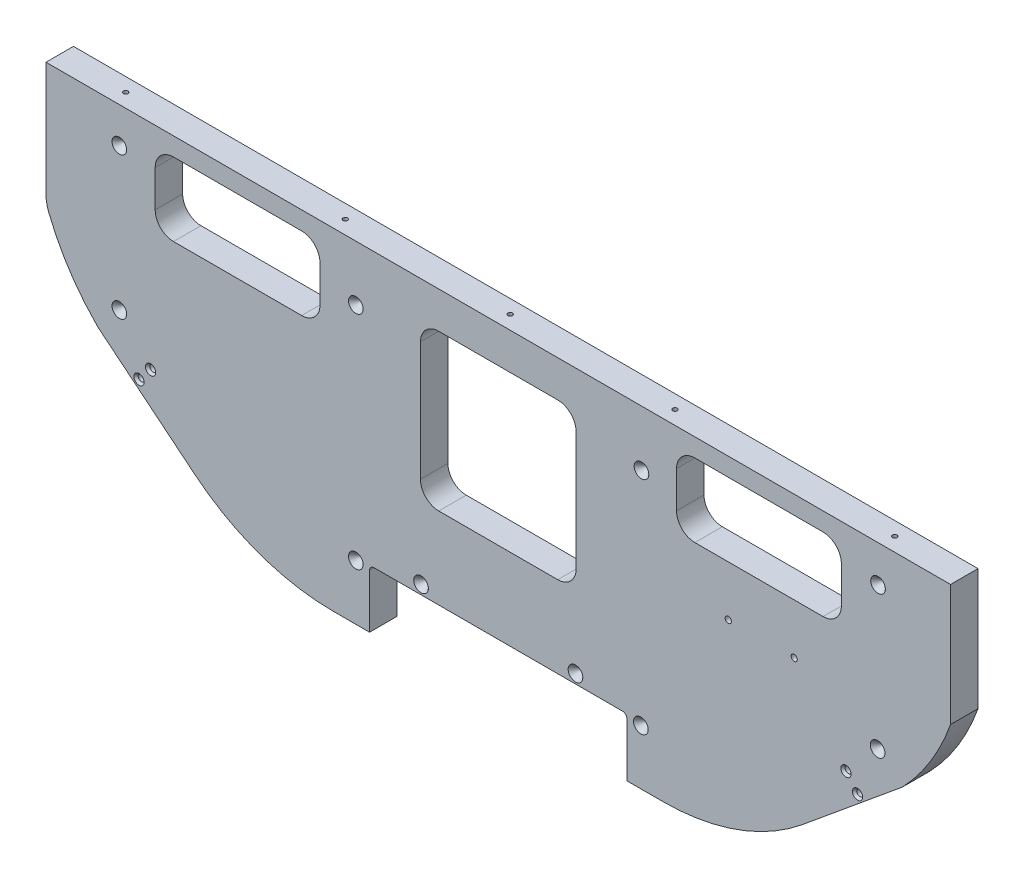
SolidWorks part; units mm, degrees
material "MDF"
ref_plane "Front Plane" through (0, 0, 0) normal (0, 0, 1) x (1, 0, 0)
ref_plane "Top Plane" through (0, 0, 0) normal (0, 1, 0) x (1, 0, 0)
ref_plane "Right Plane" through (0, 0, 0) normal (1, 0, 0) x (0, 0, -1)
sketch "Sketch1" plane through (0, 0, 0) normal (0, 0, 1) x (1, 0, 0)
  line L0 (-394.3667, -87.3125) -> (-394.3667, 23.8125) construction
  line L2 (-618.7884, -233.3625) -> (-593.7567, -233.3625) construction
  line L3 (-394.3667, -87.3125) -> (-394.3667, -3.175)
  line L4 (-497.3744, -199.0142) -> (-427.755, -141.5981)
  line L5 (-709.3267, -233.3625) -> (-593.7567, -233.3625)
  line L6 (-709.3267, -3.175) -> (-709.3267, -233.3625) construction
  line L7 (-1021.7467, -3.175) -> (-396.9067, -3.175) construction
  line L8 (-394.3667, -3.175) -> (-709.3267, -3.175)
  line L9 (-1021.7467, -3.175) -> (-396.9067, -3.175) construction
  line L10 (-976.0267, -152.2395) -> (-918.7391, -199.0142) construction
  line L11 (-1021.7467, -87.3125) -> (-1021.7467, -20.955) construction
  line L12 (-985.5517, -144.4625) -> (-918.7391, -199.0142)
  line L13 (-1021.7467, -87.3125) -> (-1021.7467, -3.175)
  line L14 (-822.3567, -233.3625) -> (-709.3267, -233.3625)
  line L15 (-709.3267, -3.175) -> (-1021.7467, -3.175)
  arc A0 (-427.755, -141.5981) -> (-394.3667, -87.3125) centre (-538.0037, -36.3792) ccw construction
  arc A1 (-593.7567, -233.3625) -> (-497.3744, -199.0142) centre (-593.7567, -80.9625) ccw construction
  arc A2 (-427.755, -141.5981) -> (-394.3667, -87.3125) centre (-538.0037, -36.3792) ccw
  arc A3 (-593.7567, -233.3625) -> (-497.3744, -199.0142) centre (-593.7567, -80.9625) ccw
  arc A4 (-918.7391, -199.0142) -> (-822.3567, -233.3625) centre (-822.3567, -80.9625) ccw construction
  arc A5 (-1021.7467, -87.3125) -> (-985.5517, -144.4625) centre (-878.1098, -36.3792) ccw construction
  arc A6 (-918.7391, -199.0142) -> (-822.3567, -233.3625) centre (-822.3567, -80.9625) ccw
  arc A7 (-1021.7467, -87.3125) -> (-985.5517, -144.4625) centre (-878.1098, -36.3792) ccw
  point P13 (-709.3267, -3.175)
extrude "Boss-Extrude1" add sketch "Sketch1" along normal blind 19.05
hole_wizard "5/64 (0.07813) Diameter Hole1" positions "Sketch2" profile "Sketch3" hole size "5/64" standard "ANSI Inch"
sketch "Sketch2" plane through (-708.0567, 15.875, 6128.5599) normal (0, 1, 0) x (1, 0, 0)
  line L1 (-1.27, 6109.5099) -> (-1.27, 6338.7449) construction
  point P0 (-262.8265, 6157.4524)
  point P6 (-98.7933, 6157.4524)
  point P18 (-262.8265, 6233.6524)
  point P19 (-98.7933, 6233.6524)
  point P22 (-262.8265, 6309.8524)
  point P23 (-98.7933, 6309.8524)
  point P24 (-267.97, 6119.0349)
  point P34 (-115.57, 6119.0349)
  point P37 (-1.27, 6119.0349)
  point P40 (113.03, 6119.0349)
  point P44 (265.43, 6119.0349)
  point P55 (96.2533, 6309.8524)
  point P56 (260.2865, 6309.8524)
  point P59 (96.2533, 6233.6524)
  point P60 (260.2865, 6233.6524)
  point P63 (96.2533, 6157.4524)
  point P64 (260.2865, 6157.4524)
sketch "Sketch3" plane through (-970.8832, 15.875, -28.8925) normal (1, 0, 0) x (0, 0, 1)
  line L0 (0, 0) -> (0, 39.0539)
  line L1 (0, 39.0539) -> (1.5875, 38.1)
  line L2 (1.5875, 38.1) -> (1.5875, 4.0177)
  line L3 (1.5875, 4.0177) -> (5.08, 0)
  line L4 (5.08, 0) -> (0, 0)
  line L5 (-1.5875, 4.0177) -> (-5.08, 0) construction
  line L6 (0, 39.0539) -> (-1.5875, 38.1) construction
  line L7 (0, -6.35) -> (0, 107.95) construction
  dimension "Hole Dia." = 3.175
  dimension "Hole Depth" = 38.1
  dimension "Near C'Sink Dia." = 10.16
  dimension "Near C'Sink Angle" = 82
  dimension "Drill Angle" = 118
hole_wizard "5/64 (0.07813) Diameter Hole2" positions "Sketch4" profile "Sketch5" hole size "5/64" standard "ANSI Inch"
sketch "Sketch4" plane through (-708.0567, 1936.854, 19.05) normal (0, 0, 1) x (-1, 0, 0)
  line L23 (262.8265, 2088.1084) -> (262.8265, 2038.7486)
  line L24 (262.8265, 2038.7486) -> (262.8265, 1989.3888)
  line L25 (262.8265, 1989.3888) -> (262.8265, 2038.7486)
  line L26 (262.8265, 2038.7486) -> (262.8265, 1989.3888)
  line L27 (262.8265, 1989.3888) -> (262.8265, 1940.029)
  line L33 (98.7933, 2170.2165) -> (98.7933, 2131.8519)
  line L35 (98.7933, 2131.8519) -> (98.7933, 2093.4873)
  line L36 (98.7933, 2093.4873) -> (98.7933, 2055.1227)
  line L37 (98.7933, 2055.1227) -> (98.7933, 2016.7581)
  line L38 (98.7933, 2016.7581) -> (98.7933, 1978.3935)
  line L39 (98.7933, 1978.3935) -> (98.7933, 1940.029)
  line L44 (89.2683, 2123.544) -> (53.561, 2123.544)
  line L46 (53.561, 2123.544) -> (17.8537, 2123.544)
  line L47 (17.8537, 2123.544) -> (-17.8537, 2123.544)
  line L48 (-17.8537, 2123.544) -> (-53.561, 2123.544)
  line L49 (-53.561, 2123.544) -> (-89.2683, 2123.544)
  line L53 (0, 2170.2165) -> (-0.3175, 1940.029) construction
  line L55 (-99.3221, 1978.6668) -> (-99.4279, 1940.3024)
  line L56 (-99.2163, 2017.0312) -> (-99.3221, 1978.6668)
  line L57 (-99.1104, 2055.3957) -> (-99.2163, 2017.0312)
  line L58 (-99.0046, 2093.7601) -> (-99.1104, 2055.3957)
  line L59 (-98.8988, 2132.1245) -> (-99.0046, 2093.7601)
  line L60 (-98.7929, 2170.489) -> (-98.8988, 2132.1245)
  line L61 (-263.3243, 1990.1145) -> (-263.4605, 1940.7549)
  line L62 (-263.1882, 2039.4741) -> (-263.3243, 1990.1145)
  line L63 (-263.3243, 1990.1145) -> (-263.1882, 2039.4741)
  line L64 (-263.1882, 2039.4741) -> (-263.3243, 1990.1145)
  line L65 (-263.052, 2088.8338) -> (-263.1882, 2039.4741)
  point P71 (262.8265, 1964.7089)
  point P79 (262.8265, 2063.4285)
  point P95 (98.7933, 2131.8519)
  point P103 (98.7933, 1978.3935)
  point P126 (53.561, 2123.544)
  point P134 (-53.561, 2123.544)
  point P162 (-99.3221, 1978.6668)
  point P166 (-98.8988, 2132.1245)
  point P167 (-263.1201, 2064.1539)
  point P169 (-263.3924, 1965.4347)
sketch "Sketch5" plane through (-444.6643, -28.5807, 19.05) normal (1, 0, 0) x (0, -1, 0)
  line L0 (0, 0) -> (0, 38.6962)
  line L1 (0, 38.6962) -> (0.9923, 38.1)
  line L2 (0.9923, 38.1) -> (0.9923, 4.7024)
  line L3 (0.9923, 4.7024) -> (5.08, 0)
  line L4 (5.08, 0) -> (0, 0)
  line L5 (-0.9923, 4.7024) -> (-5.08, 0) construction
  line L6 (0, 38.6962) -> (-0.9923, 38.1) construction
  line L7 (0, -6.35) -> (0, 107.95) construction
  dimension "Hole Dia." = 1.9845
  dimension "Hole Depth" = 38.1
  dimension "Near C'Sink Dia." = 10.16
  dimension "Near C'Sink Angle" = 82
  dimension "Drill Angle" = 118
sketch "Sketch6" plane through (0, 0, 0) normal (0, 0, -1) x (-1, 0, 0)
  line L1 (797.325, -233.3625) -> (618.7884, -233.3625)
  line L2 (797.325, -233.3625) -> (797.325, -193.04)
  line L3 (797.325, -193.04) -> (618.7884, -193.04)
  line L4 (618.7884, -233.3625) -> (618.7884, -193.04)
extrude "Cut-Extrude1" cut sketch "Sketch6" against normal up to next
fillet "Fillet1" radius 25.4 2 edges at (-985.5517, -144.4625, 9.525) (-1021.7467, -87.3125, 9.525)
hole_wizard "#6 Clearance Hole1" positions "Sketch7" profile "Sketch8" hole size "#6" standard "ANSI Inch" end condition up to next
sketch "Sketch7" plane through (0, 0, 19.05) normal (0, 0, 1) x (1, 0, 0)
  arc A0 (-504.7297, -98.0667) -> (-504.7297, -104.8742) centre (-502.7993, -101.4705) ccw construction
  arc A1 (-550.4497, -98.0667) -> (-550.4497, -104.8742) centre (-548.5193, -101.4705) ccw construction
  point P0 (-502.7993, -101.4705)
  point P2 (-548.5193, -101.4705)
sketch "Sketch8" plane through (-502.7993, -101.4705, 19.05) normal (1, 0, 0) x (0, -1, 0)
  line L0 (0, 0) -> (0, 19.05)
  line L1 (0, 19.05) -> (2.1526, 19.05)
  line L2 (2.1526, 19.05) -> (2.1526, 0)
  line L5 (2.1526, 0) -> (0, 0)
  line L11 (0, -6.35) -> (0, 107.95) construction
  dimension "Thru Hole Dia." = 4.3053
  dimension "Thru Hole Depth" = 19.05
hole_wizard "CSK for #6 Flat Head Machine Screw (100)1" positions "Sketch9" profile "Sketch10" countersink size "#6" standard "ANSI Inch" end condition up to next
sketch "Sketch9" plane through (0, 0, 19.05) normal (0, 0, 1) x (1, 0, 0)
  point P0 (-957.2382, -161.4319)
  point P3 (-949.206, -151.5944)
  point P6 (-466.9052, -151.5924)
  point P9 (-458.8731, -161.4298)
sketch "Sketch10" plane through (-957.2382, -161.4319, 19.05) normal (1, 0, 0) x (0, -1, 0)
  line L0 (0, 0) -> (0, 19.05)
  line L1 (0, 19.05) -> (2.1526, 19.05)
  line L2 (2.1526, 19.05) -> (2.1526, 1.5998)
  line L3 (2.1526, 1.5998) -> (3.5433, 0)
  line L5 (3.5433, 0) -> (0, 0)
  line L6 (-2.1526, 1.5998) -> (-3.5433, 0) construction
  line L11 (0, -6.35) -> (0, 107.95) construction
  dimension "Thru Hole Dia." = 4.3053
  dimension "Thru Hole Depth" = 19.05
  dimension "Near C'Sink Dia." = 7.0866
  dimension "Near C'Sink Angle" = 82
sketch "Sketch12" plane through (0, 0, 19.05) normal (0, 0, 1) x (1, 0, 0)
  line L0 (-708.0567, -193.04) -> (-708.0567, -3.175) construction
  line L1 (-797.325, -193.04) -> (-618.7884, -193.04) construction
  line L2 (-394.3667, -3.175) -> (-1021.7467, -3.175) construction
  line L3 (-970.8832, -27.8549) -> (-806.85, -27.8549) construction
  line L4 (-806.85, -41.5396) -> (-806.85, -27.8549) construction
  line L5 (-584.3968, -15.875) -> (-470.0968, -15.875)
  line L6 (-831.7166, -66.675) -> (-946.0166, -66.675)
  line L7 (-831.7166, -66.675) -> (-831.7166, -15.875)
  line L8 (-831.7166, -15.875) -> (-946.0166, -15.875)
  line L9 (-946.0166, -66.675) -> (-946.0166, -15.875)
  line L10 (-831.7166, -66.675) -> (-946.0166, -15.875) construction
  line L11 (-831.7166, -15.875) -> (-946.0166, -66.675) construction
  line L12 (-470.0968, -66.675) -> (-470.0968, -15.875)
  line L13 (-584.3968, -66.675) -> (-470.0968, -66.675)
  line L14 (-584.3968, -66.675) -> (-584.3968, -15.875)
  line L15 (-394.3667, -3.175) -> (-1021.7467, -3.175) construction
  line L16 (-654.0817, -136.525) -> (-762.0317, -136.525)
  line L17 (-654.0817, -136.525) -> (-654.0817, -28.575)
  line L18 (-654.0817, -28.575) -> (-762.0317, -28.575)
  line L19 (-762.0317, -136.525) -> (-762.0317, -28.575)
  line L20 (-654.0817, -136.525) -> (-762.0317, -28.575) construction
  line L21 (-654.0817, -28.575) -> (-762.0317, -136.525) construction
  point P9 (-888.8666, -27.8549)
  point P10 (-888.8666, -41.275)
  point P20 (-708.0567, -82.55)
  dimension "D1" = 114.3
  dimension "D2" = 50.8
  dimension "D3" = 12.7
  dimension "D4" = 107.95
  dimension "D5" = 107.95
  dimension "D6" = 25.4
extrude "Cut-Extrude2" cut sketch "Sketch12" against normal through all
fillet "Fillet2" radius 12.7 12 edges at (-584.3968, -66.675, 9.525) (-584.3968, -15.875, 9.525) (-470.0968, -15.875, 9.525) (-470.0968, -66.675, 9.525) (-654.0817, -136.525, 9.525) (-654.0817, -28.575, 9.525) (-762.0317, -28.575, 9.525) (-762.0317, -136.525, 9.525) (-946.0166, -66.675, 9.525) (-946.0166, -15.875, 9.525) (-831.7166, -15.875, 9.525) (-831.7166, -66.675, 9.525)
fillet "Fillet3" radius 3.175 2 edges at (-618.7884, -193.04, 9.525) (-797.325, -193.04, 9.525)
